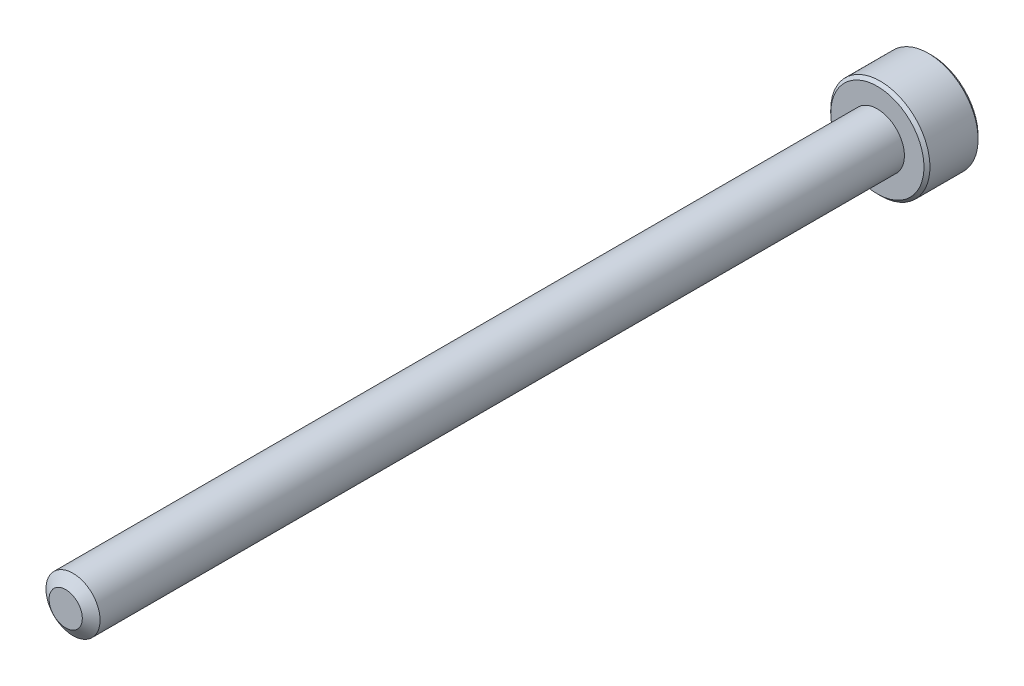
SolidWorks part; units mm, degrees
ref_plane "Front Plane" through (0, 0, 0) normal (0, 0, 1) x (1, 0, 0)
ref_plane "Top Plane" through (0, 0, 0) normal (0, 1, 0) x (1, 0, 0)
ref_plane "Right Plane" through (0, 0, 0) normal (1, 0, 0) x (0, 0, -1)
sketch "Sketch1" plane through (0, 0, 0) normal (0, 0, 1) x (1, 0, 0)
  circle A0 centre (0, 0) radius 1.5
  dimension "OD" = 3
extrude "Extrude1" add sketch "Sketch1" against normal blind 45
sketch "Sketch2" plane through (0, 0, 0) normal (0, 0, 1) x (1, 0, 0)
  circle A0 centre (0, 0) radius 1.5 construction
  circle A1 centre (0, 0) radius 1.5
curve "Helix/Spiral1" pitch 0.5 height 45.5 turns 91 parameters "pitch"=0.5
sketch "Sketch3" plane through (0, 0, 0) normal (1, 0, 0) x (0, 0, -1)
  line L0 (-0.4375, 1.5) -> (-0.25, 1.1752)
  line L1 (-0.25, 1.1752) -> (-0.1875, 1.1752)
  line L2 (-0.1875, 1.1752) -> (0, 1.5)
  line L3 (-0.4375, 1.5) -> (0, 1.5)
  line L4 (-0.2187, 1.5) -> (-0.2187, 1.1752) construction
  line L5 (-0.3437, 1.3376) -> (-0.0937, 1.3376) construction
  line L6 (0, 1.5) -> (0, -1.5) construction
  line L7 (0, -1.5) -> (45, -1.5) construction
  point P11 (2.25, -1.5)
  dimension "D1" = 0.0625
  dimension "D2" = 0.25
  dimension "D3" = 60
  dimension "D4" = 2.25
sweep "Cut-Sweep1" [suppressed] cut profiles "Sketch3" path "Helix/Spiral1"
sketch "Sketch4" plane through (0, 0, 0) normal (1, 0, 0) x (0, 0, -1)
  line L0 (0.4053, 1.5) -> (0, 0.9212)
  line L1 (0, 0.9212) -> (0, 1.5)
  line L2 (0.4053, 1.5) -> (0, 1.5)
  line L3 (-0.4375, 1.5) -> (0, 1.5) construction
  line L4 (0, 0) -> (7.0209, 0) construction
  dimension "D1" = 55
  dimension "D2" = 0.254
revolve "Cut-Revolve1" cut sketch "Sketch4" angle 360 about L4
sketch "Sketch5" [suppressed] plane through (0, 0, 0) normal (1, 0, 0) x (0, 0, -1)
  line L0 (45, -1.1822) -> (45, 1.0703) construction
  line L1 (45, 1.5) -> (18.1202, 1.5)
  line L2 (45, 1.5) -> (45, 0)
  line L3 (45, 0) -> (18, 0)
  line L4 (18, 1.1698) -> (18, 0)
  line L5 (18.1202, 1.5) -> (18, 1.1698)
  line L6 (0, 0) -> (9.9695, 0) construction
  point P3 (18, 1.5)
  point P10 (18, 1.5)
  dimension "D1" = 0.3302
  dimension "Thread min" = 18
  dimension "D3" = 20
revolve "partially thread" [suppressed] add sketch "Sketch5" angle 360 about L6
sketch "Sketch6" plane through (0, 0, -45) normal (0, 0, -1) x (-1, 0, 0)
  circle A0 centre (0, 0) radius 2.75
  dimension "head dia" = 5.5
extrude "Extrude2" add sketch "Sketch6" along normal blind 3
sketch "Sketch7" plane through (0, 0, -48) normal (0, 0, -1) x (-1, 0, 0)
  line L1 (0, 1.4434) -> (-1.25, 0.7217)
  line L2 (-1.25, 0.7217) -> (-1.25, -0.7217)
  line L3 (-1.25, -0.7217) -> (0, -1.4434)
  line L4 (0, -1.4434) -> (1.25, -0.7217)
  line L5 (1.25, -0.7217) -> (1.25, 0.7217)
  line L6 (1.25, 0.7217) -> (0, 1.4434)
  circle A0 centre (0, 0) radius 1.25 construction
  dimension "hex dia" = 2.5
extrude "Cut-Extrude1" cut sketch "Sketch7" against normal blind 1.875
sketch "Sketch8" plane through (0, 0, -48) normal (0, 0, -1) x (-1, 0, 0)
  circle A0 centre (0, 0) radius 1.4434
extrude "Cut-Extrude2" cut sketch "Sketch8" against normal through all draft 45
chamfer "Chamfer1" distance 0.165 angle 45 2 edges at (-2.75, 0, -48) (-2.75, 0, -45)
sketch "Sketch9" plane through (0, 0, 0) normal (1, 0, 0) x (0, 0, -1)
  line L0 (0, 1.5) -> (0, -1.5) construction
  line L1 (2.75, 1.5) -> (2.75, -1.5) construction
  dimension "D1" = 2.75
sketch "Sketch10" plane through (0, 0, 0) normal (1, 0, 0) x (0, 0, -1)
  line L0 (45, 1.5) -> (45, 0)
  line L1 (45, 1.5) -> (44.875, 1.5)
  line L2 (44.875, 1.5) -> (44.2537, 0)
  line L3 (45, 0) -> (44.2537, 0)
  line L4 (45, 2.585) -> (45, -2.585) construction
  dimension "D1" = 22.5
  dimension "D2" = 0.125
revolve "Revolve1" [suppressed] add sketch "Sketch10" angle 360 about L3
equation "\"D3@Helix/Spiral1\" = \"screw length@Extrude1\"+\"pitch@Helix/Spiral1\""
equation "\"D1@Sketch3\" = \"pitch@Helix/Spiral1\"*.125"
equation "\"D2@Sketch3\" = \"pitch@Helix/Spiral1\"*.5"
equation "\"D1@Cut-Extrude1\" = \"hex dia@Sketch7\"*.75"
equation "\"D1@Chamfer1\" = \"head dia@Sketch6\"*.03"
equation "\"D1@Sketch9\" = \"pitch@Helix/Spiral1\"*5.5"
equation "\"D2@Sketch10\" = \"pitch@Helix/Spiral1\"*.25"
equation "\"D4@Sketch3\" = \"pitch@Helix/Spiral1\"*4.50"
